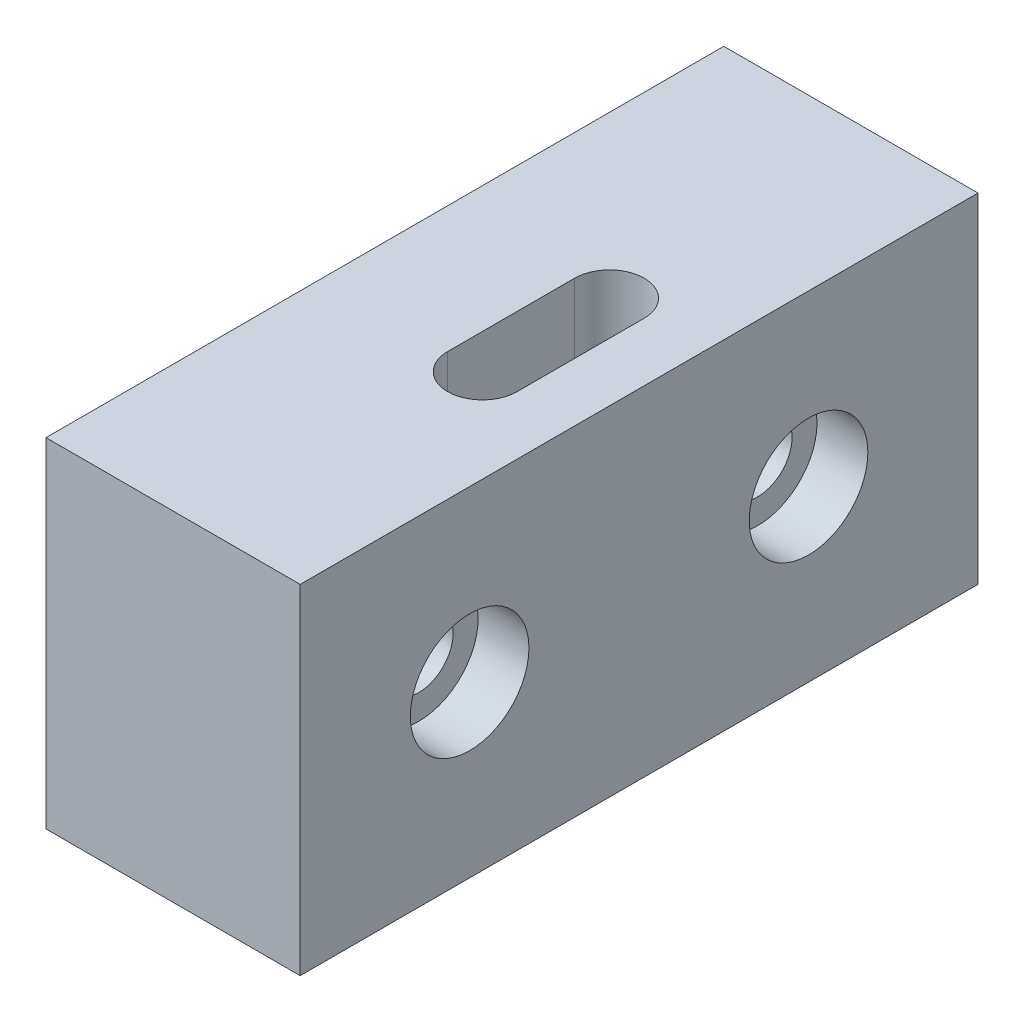
SolidWorks part; units mm, degrees
ref_plane "Front Plane" through (0, 0, 0) normal (0, 0, 1) x (1, 0, 0)
ref_plane "Top Plane" through (0, 0, 0) normal (0, 1, 0) x (1, 0, 0)
ref_plane "Right Plane" through (0, 0, 0) normal (1, 0, 0) x (0, 0, -1)
sketch "Sketch1" plane through (0, 0, 0) normal (0, 0, 1) x (1, 0, 0)
  line L5 (-15, -20) -> (15, -20)
  line L6 (-15, -20) -> (-15, 20)
  line L11 (-15, 20) -> (15, 20)
  line L12 (15, -20) -> (15, 20)
  line L17 (-15, -20) -> (15, 20) construction
  line L18 (-15, 20) -> (15, -20) construction
  point P0 (0, 0)
  dimension "D1" = 30
  dimension "D2" = 40
extrude "Boss-Extrude1" add sketch "Sketch1" along normal blind 40 and the other way blind 40 contours L11 L12 L5 L6 | L5 L12 L11 L6 region at (0, 0, 0)
sketch "Sketch2" plane through (0, 0, 0) normal (1, 0, 0) x (0, 0, -1)
  line L0 (-20, 0) -> (20, 0) construction
  circle A0 centre (-20, 0) radius 4.05
  circle A1 centre (20, 0) radius 4.05
  dimension "D2" = 8.1
  dimension "D1" = 40
extrude "Cut-Extrude1" cut sketch "Sketch2" against normal blind 80 and the other way blind 80
sketch "Sketch3" plane through (0, 0, 0) normal (1, 0, 0) x (0, 0, -1)
  circle A0 centre (-20, 0) radius 7
  circle A1 centre (20, 0) radius 7
  dimension "D1" = 14
extrude "Cut-Extrude2" cut sketch "Sketch3" against normal blind 6 from surface starting at face at (15, 0, 15.95)
sketch "Sketch4" plane through (0, 0, 0) normal (0, 1, 0) x (1, 0, 0)
  line L0 (4, -7.5) -> (4, 7.5) construction
  line L1 (-0.1, -7.5) -> (-0.1, 7.5)
  line L2 (8.1, -7.5) -> (8.1, 7.5)
  line L3 (0, 0) -> (4, 0) construction
  arc A0 (-0.1, -7.5) -> (8.1, -7.5) centre (4, -7.5) ccw
  arc A1 (8.1, 7.5) -> (-0.1, 7.5) centre (4, 7.5) ccw
  point P2 (4, 0)
  dimension "D1" = 15
  dimension "D2" = 8.2
  dimension "D3" = 4
extrude "Cut-Extrude3" cut sketch "Sketch4" against normal blind 36 and the other way blind 36
